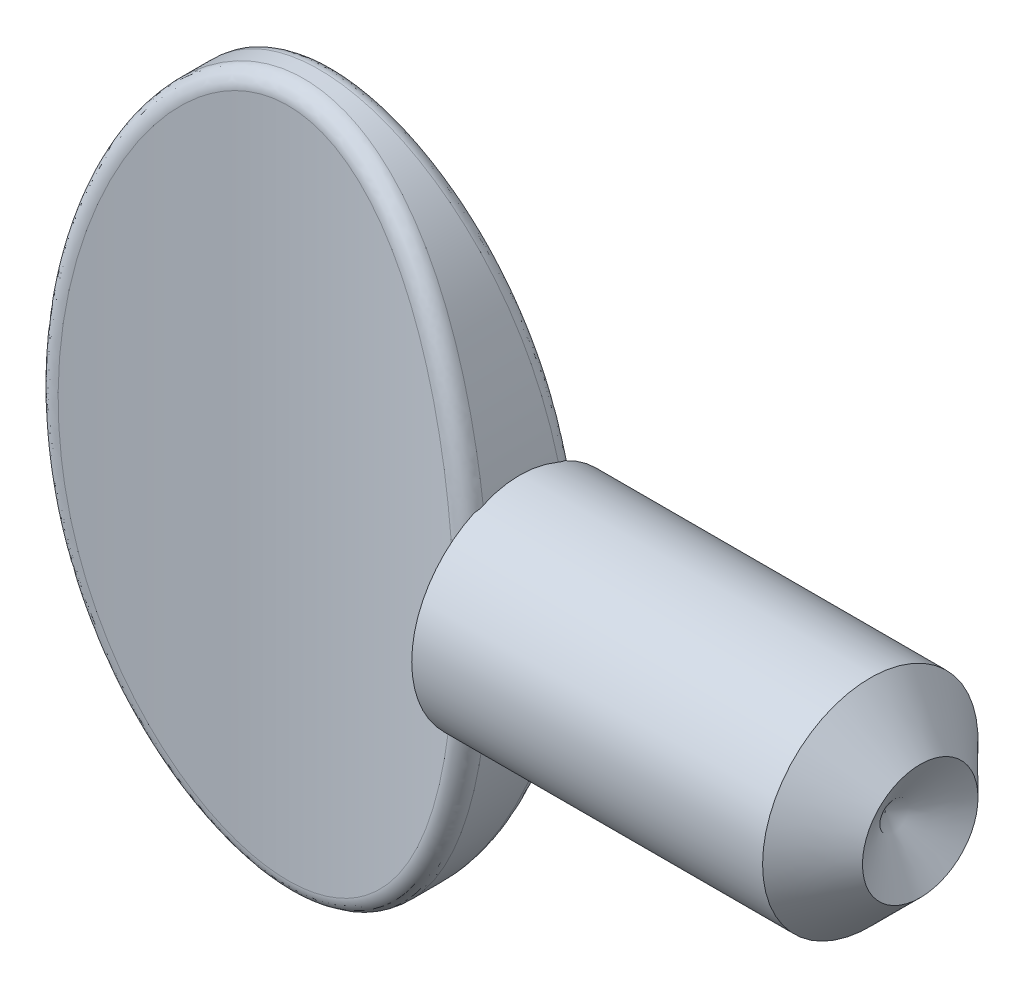
SolidWorks part; units mm, degrees
ref_plane "Front" through (0, 0, 0) normal (0, 0, 1) x (1, 0, 0)
ref_plane "Top" through (0, 0, 0) normal (0, 1, 0) x (1, 0, 0)
ref_plane "Right" through (0, 0, 0) normal (1, 0, 0) x (0, 0, -1)
ref_axis "Axis1" through (-50, 0, 0) along (1, 0, 0)
sketch "Sketch1" plane through (0, 0, 0) normal (0, 0, 1) x (1, 0, 0)
  line L0 (0, 0) -> (9.906, 0) construction
  line L1 (4.7413, -1.7526) -> (4.7413, 1.7526)
  line L2 (4.7413, -1.7526) -> (3.3847, -1.7526) construction
  ellipse E0 centre (0, 0) end of major axis (0, -5.715) minor radius 3.556
  dimension "D2" = 1.1853
  dimension "B" = 7.112
  dimension "L" = 6.35
extrude "Extrude1" add sketch "Sketch1" along normal mid plane 2.032
sketch "Sketch2" plane through (0, 0, 0) normal (0, 1, 0) x (1, 0, 0)
  line L0 (3.556, 1.016) -> (-3.556, 1.016) construction
  line L1 (0, 0) -> (0, 1.1721) construction
  line L2 (-1.7991, 0) -> (2.0444, 0) construction
  line L3 (-3.556, -1.016) -> (3.556, -1.016) construction
  line L6 (-3.556, 1.016) -> (-3.556, -1.016)
  line L7 (3.556, 1.016) -> (3.556, -1.016)
  arc A0 (-3.556, 1.016) -> (3.556, 1.016) centre (0, 10.6553) ccw
  arc A1 (-3.556, -1.016) -> (3.556, -1.016) centre (0, -10.6553) cw
extrude "Cut-Extrude1" cut sketch "Sketch2" against normal through all and the other way through all flip side to cut
fillet "Fillet3" radius 0.254 2 edges at (-3.4679, -1.2641, 0.984) (0.2073, 5.7053, -0.3831)
sketch "Sketch3" plane through (0, 0, 0) normal (0, 1, 0) x (1, 0, 0)
  line L0 (9.0932, 1.7526) -> (9.906, 0.9398)
  line L1 (0, 0) -> (21.0288, 0) construction
  line L2 (0, 0) -> (9.906, 0) construction
  line L3 (4.7413, 1.7526) -> (4.7413, 0) construction
  line L4 (4.7413, 1.7526) -> (9.0932, 1.7526)
  line L5 (9.906, 0.9398) -> (9.3413, 0)
  line L6 (4.7413, 1.7526) -> (3.3847, 1.7526)
  line L7 (2.5775, 0.7096) -> (2.5775, 0)
  line L8 (3.3847, 0) -> (3.3847, 1.7526) construction
  line L9 (2.5775, 0) -> (9.3413, 0)
  arc A0 (3.3847, 1.7526) -> (2.5775, 0.7096) centre (2.3072, 1.7526) cw
  arc A3 (-3.556, 1.016) -> (3.556, 1.016) centre (0, 10.6553) ccw construction
  dimension "D1" = 45
  dimension "D2" = 59
revolve "Revolve1" add sketch "Sketch3" angle 360 about L0
cosmetic thread "Cosmetic Thread1" [suppressed]
sketch "Sketch4" plane through (0, 0, 0) normal (0, 0, 1) x (1, 0, 0)
  line L0 (0, 0) -> (27.7993, 0) construction
  line L1 (8.8879, 1.7526) -> (9.0932, 1.397)
  line L2 (9.0932, 1.397) -> (9.2985, 1.7526)
  line L3 (9.2985, 1.7526) -> (9.2985, 2.1632)
  line L4 (9.2985, 2.1632) -> (8.8879, 2.1632)
  line L5 (8.8879, 2.1632) -> (8.8879, 1.7526)
  line L6 (9.0932, 1.7526) -> (9.0932, -1.7526) construction
  dimension "D1" = 2.794
  dimension "D2" = 3.5052
revolve "Cut-Revolve10" [suppressed] cut sketch "Sketch4" angle 360 about L0
pattern_linear "LPattern10" [suppressed] count 11 along (-1, 0, 0) of bodies 109
equation "\"D2@Sketch1\" = \"B@Sketch1\" / 6"
equation "\"D1@Fillet3\" = \"C1@Sketch2\" / 3"
equation "\"DIA@Sketch3\" = \"D@Sketch1\""
equation "\"D1@Cosmetic Thread1\" = \"L@Sketch1\" - (  \"D@Sketch1\" - \"cup_dia@Sketch3\" )  / 2"
equation "\"D1@Sketch4\" = \"D2@Cosmetic Thread1\""
equation "\"D2@Sketch4\" = \"DIA@Sketch3\""
equation "\"D1@LPattern10\" = \"D1@Cosmetic Thread1\" / \"P@LPattern10\" "
